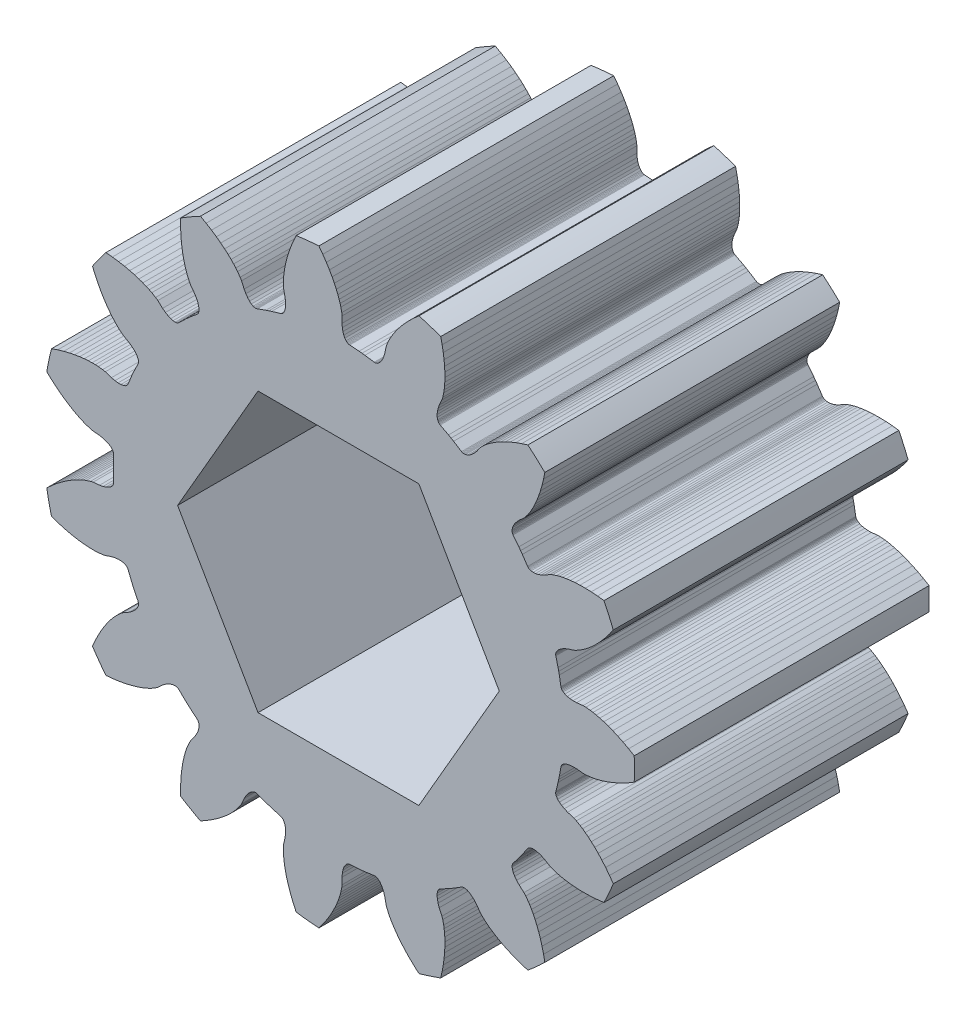
SolidWorks part; units mm, degrees
ref_plane "Front Plane" through (0, 0, 0) normal (0, 0, 1) x (1, 0, 0)
ref_plane "Top Plane" through (0, 0, 0) normal (0, 1, 0) x (1, 0, 0)
ref_plane "Right Plane" through (0, 0, 0) normal (1, 0, 0) x (0, 0, -1)
sketch "Model" plane through (0, 0, 0) normal (0, 0, 1) x (1, 0, 0)
  line L0 (11.6767, 4.5035) -> (11.5103, 4.2885)
  line L1 (11.5103, 4.2885) -> (11.3474, 4.0954)
  line L2 (11.3474, 4.0954) -> (11.1891, 3.9228)
  line L3 (11.1891, 3.9228) -> (11.0382, 3.7715)
  line L4 (11.0382, 3.7715) -> (10.8925, 3.6371)
  line L5 (10.8925, 3.6371) -> (10.7549, 3.5206)
  line L6 (10.7549, 3.5206) -> (10.6294, 3.4231)
  line L7 (10.6294, 3.4231) -> (10.5151, 3.3416)
  line L8 (10.5151, 3.3416) -> (10.4119, 3.2743)
  line L9 (10.4119, 3.2743) -> (10.2465, 3.1803)
  line L10 (10.2465, 3.1803) -> (10.1399, 3.1309)
  line L11 (10.1399, 3.1309) -> (9.873, 3.0467)
  line L12 (9.873, 3.0467) -> (9.7318, 2.9862)
  line L13 (9.7318, 2.9862) -> (9.613, 2.9201)
  line L14 (9.613, 2.9201) -> (9.5168, 2.8501)
  line L15 (9.5168, 2.8501) -> (9.4433, 2.778)
  line L16 (9.4433, 2.778) -> (9.3924, 2.7056)
  line L17 (9.3924, 2.7056) -> (9.3754, 2.6698)
  line L18 (9.3754, 2.6698) -> (9.364, 2.6346)
  line L19 (9.364, 2.6346) -> (9.3582, 2.6002)
  line L20 (9.3582, 2.6002) -> (9.3579, 2.5668)
  line L21 (9.3579, 2.5668) -> (9.363, 2.5346)
  line L22 (9.363, 2.5346) -> (9.4607, 2.1415)
  line L23 (9.4607, 2.1415) -> (9.488, 2.0167)
  line L24 (9.488, 2.0167) -> (9.5138, 1.8917)
  line L25 (9.5138, 1.8917) -> (9.5845, 1.4928)
  line L26 (9.5845, 1.4928) -> (9.5928, 1.4613)
  line L27 (9.5928, 1.4613) -> (9.6067, 1.4309)
  line L28 (9.6067, 1.4309) -> (9.626, 1.4019)
  line L29 (9.626, 1.4019) -> (9.6508, 1.3743)
  line L30 (9.6508, 1.3743) -> (9.6808, 1.3485)
  line L31 (9.6808, 1.3485) -> (9.7568, 1.3031)
  line L32 (9.7568, 1.3031) -> (9.8533, 1.2671)
  line L33 (9.8533, 1.2671) -> (9.9696, 1.2423)
  line L34 (9.9696, 1.2423) -> (10.105, 1.2303)
  line L35 (10.105, 1.2303) -> (10.2586, 1.2324)
  line L36 (10.2586, 1.2324) -> (10.5367, 1.2641)
  line L37 (10.5367, 1.2641) -> (10.6542, 1.2623)
  line L38 (10.6542, 1.2623) -> (10.8435, 1.2437)
  line L39 (10.8435, 1.2437) -> (10.9652, 1.2242)
  line L40 (10.9652, 1.2242) -> (11.1027, 1.1962)
  line L41 (11.1027, 1.1962) -> (11.2571, 1.1582)
  line L42 (11.2571, 1.1582) -> (11.4301, 1.1077)
  line L43 (11.4301, 1.1077) -> (11.6179, 1.0442)
  line L44 (11.6179, 1.0442) -> (11.8173, 0.9674)
  line L45 (11.8173, 0.9674) -> (12.0321, 0.8741)
  line L46 (12.0321, 0.8741) -> (12.2594, 0.764)
  line L47 (12.2594, 0.764) -> (12.499, 0.6352)
  line L48 (12.499, 0.6352) -> (12.7405, 0.492)
  line L49 (12.7405, -0.492) -> (12.499, -0.6352)
  line L50 (12.499, -0.6352) -> (12.2594, -0.764)
  line L51 (12.2594, -0.764) -> (12.0321, -0.8741)
  line L52 (12.0321, -0.8741) -> (11.8173, -0.9674)
  line L53 (11.8173, -0.9674) -> (11.6179, -1.0442)
  line L54 (11.6179, -1.0442) -> (11.4301, -1.1077)
  line L55 (11.4301, -1.1077) -> (11.2571, -1.1582)
  line L56 (11.2571, -1.1582) -> (11.1027, -1.1962)
  line L57 (11.1027, -1.1962) -> (10.9652, -1.2242)
  line L58 (10.9652, -1.2242) -> (10.8435, -1.2437)
  line L59 (10.8435, -1.2437) -> (10.6542, -1.2623)
  line L60 (10.6542, -1.2623) -> (10.5367, -1.2641)
  line L61 (10.5367, -1.2641) -> (10.2586, -1.2324)
  line L62 (10.2586, -1.2324) -> (10.105, -1.2303)
  line L63 (10.105, -1.2303) -> (9.9696, -1.2423)
  line L64 (9.9696, -1.2423) -> (9.8533, -1.2671)
  line L65 (9.8533, -1.2671) -> (9.7568, -1.3031)
  line L66 (9.7568, -1.3031) -> (9.6808, -1.3485)
  line L67 (9.6808, -1.3485) -> (9.6508, -1.3743)
  line L68 (9.6508, -1.3743) -> (9.626, -1.4019)
  line L69 (9.626, -1.4019) -> (9.6067, -1.4309)
  line L70 (9.6067, -1.4309) -> (9.5928, -1.4613)
  line L71 (9.5928, -1.4613) -> (9.5845, -1.4928)
  line L72 (9.5845, -1.4928) -> (9.5138, -1.8917)
  line L73 (9.5138, -1.8917) -> (9.488, -2.0167)
  line L74 (9.488, -2.0167) -> (9.4607, -2.1415)
  line L75 (9.4607, -2.1415) -> (9.363, -2.5346)
  line L76 (9.363, -2.5346) -> (9.3579, -2.5668)
  line L77 (9.3579, -2.5668) -> (9.3582, -2.6002)
  line L78 (9.3582, -2.6002) -> (9.364, -2.6346)
  line L79 (9.364, -2.6346) -> (9.3754, -2.6698)
  line L80 (9.3754, -2.6698) -> (9.3924, -2.7056)
  line L81 (9.3924, -2.7056) -> (9.4433, -2.778)
  line L82 (9.4433, -2.778) -> (9.5168, -2.8501)
  line L83 (9.5168, -2.8501) -> (9.613, -2.9201)
  line L84 (9.613, -2.9201) -> (9.7318, -2.9862)
  line L85 (9.7318, -2.9862) -> (9.873, -3.0467)
  line L86 (9.873, -3.0467) -> (10.1399, -3.1309)
  line L87 (10.1399, -3.1309) -> (10.2465, -3.1803)
  line L88 (10.2465, -3.1803) -> (10.4119, -3.2743)
  line L89 (10.4119, -3.2743) -> (10.5151, -3.3416)
  line L90 (10.5151, -3.3416) -> (10.6294, -3.4231)
  line L91 (10.6294, -3.4231) -> (10.7549, -3.5206)
  line L92 (10.7549, -3.5206) -> (10.8925, -3.6371)
  line L93 (10.8925, -3.6371) -> (11.0382, -3.7715)
  line L94 (11.0382, -3.7715) -> (11.1891, -3.9228)
  line L95 (11.1891, -3.9228) -> (11.3474, -4.0954)
  line L96 (11.3474, -4.0954) -> (11.5103, -4.2885)
  line L97 (11.5103, -4.2885) -> (11.6767, -4.5035)
  line L98 (11.6767, -4.5035) -> (11.8391, -4.7326)
  line L99 (11.4389, -5.6315) -> (11.16, -5.6641)
  line L100 (11.16, -5.6641) -> (10.8888, -5.6843)
  line L101 (10.8888, -5.6843) -> (10.6364, -5.6925)
  line L102 (10.6364, -5.6925) -> (10.4021, -5.6903)
  line L103 (10.4021, -5.6903) -> (10.1888, -5.6793)
  line L104 (10.1888, -5.6793) -> (9.9914, -5.661)
  line L105 (9.9914, -5.661) -> (9.8128, -5.6367)
  line L106 (9.8128, -5.6367) -> (9.6563, -5.6087)
  line L107 (9.6563, -5.6087) -> (9.5193, -5.5783)
  line L108 (9.5193, -5.5783) -> (9.4002, -5.5466)
  line L109 (9.4002, -5.5466) -> (9.2197, -5.4866)
  line L110 (9.2197, -5.4866) -> (9.1116, -5.4405)
  line L111 (9.1116, -5.4405) -> (8.8704, -5.2984)
  line L112 (8.8704, -5.2984) -> (8.731, -5.234)
  line L113 (8.731, -5.234) -> (8.6024, -5.1899)
  line L114 (8.6024, -5.1899) -> (8.486, -5.1653)
  line L115 (8.486, -5.1653) -> (8.3833, -5.1589)
  line L116 (8.3833, -5.1589) -> (8.2954, -5.1695)
  line L117 (8.2954, -5.1695) -> (8.2574, -5.1808)
  line L118 (8.2574, -5.1808) -> (8.2236, -5.1959)
  line L119 (8.2236, -5.1959) -> (8.1941, -5.2146)
  line L120 (8.1941, -5.2146) -> (8.1691, -5.2367)
  line L121 (8.1691, -5.2367) -> (8.1487, -5.2621)
  line L122 (8.1487, -5.2621) -> (7.9219, -5.5977)
  line L123 (7.9219, -5.5977) -> (7.8475, -5.7015)
  line L124 (7.8475, -5.7015) -> (7.7717, -5.8044)
  line L125 (7.7717, -5.8044) -> (7.5226, -6.1238)
  line L126 (7.5226, -6.1238) -> (7.5048, -6.151)
  line L127 (7.5048, -6.151) -> (7.4915, -6.1817)
  line L128 (7.4915, -6.1817) -> (7.4828, -6.2155)
  line L129 (7.4828, -6.2155) -> (7.4789, -6.2523)
  line L130 (7.4789, -6.2523) -> (7.4799, -6.2919)
  line L131 (7.4799, -6.2919) -> (7.4969, -6.3788)
  line L132 (7.4969, -6.3788) -> (7.5348, -6.4746)
  line L133 (7.5348, -6.4746) -> (7.5942, -6.5776)
  line L134 (7.5942, -6.5776) -> (7.6759, -6.6863)
  line L135 (7.6759, -6.6863) -> (7.7802, -6.799)
  line L136 (7.7802, -6.799) -> (7.9899, -6.9845)
  line L137 (7.9899, -6.9845) -> (8.0671, -7.073)
  line L138 (8.0671, -7.073) -> (8.1799, -7.2261)
  line L139 (8.1799, -7.2261) -> (8.2469, -7.3296)
  line L140 (8.2469, -7.3296) -> (8.3182, -7.4505)
  line L141 (8.3182, -7.4505) -> (8.3931, -7.5907)
  line L142 (8.3931, -7.5907) -> (8.4714, -7.753)
  line L143 (8.4714, -7.753) -> (8.5499, -7.9351)
  line L144 (8.5499, -7.9351) -> (8.6262, -8.1346)
  line L145 (8.6262, -8.1346) -> (8.7007, -8.3567)
  line L146 (8.7007, -8.3567) -> (8.7709, -8.5993)
  line L147 (8.7709, -8.5993) -> (8.8355, -8.8635)
  line L148 (8.8355, -8.8635) -> (8.8906, -9.1388)
  line L149 (8.1594, -9.7972) -> (7.8914, -9.7136)
  line L150 (7.8914, -9.7136) -> (7.6354, -9.6217)
  line L151 (7.6354, -9.6217) -> (7.4015, -9.5265)
  line L152 (7.4015, -9.5265) -> (7.1884, -9.4292)
  line L153 (7.1884, -9.4292) -> (6.9979, -9.3325)
  line L154 (6.9979, -9.3325) -> (6.8251, -9.2354)
  line L155 (6.8251, -9.2354) -> (6.6718, -9.1406)
  line L156 (6.6718, -9.1406) -> (6.5402, -9.0514)
  line L157 (6.5402, -9.0514) -> (6.4274, -8.9679)
  line L158 (6.4274, -8.9679) -> (6.3315, -8.8905)
  line L159 (6.3315, -8.8905) -> (6.191, -8.7623)
  line L160 (6.191, -8.7623) -> (6.111, -8.6762)
  line L161 (6.111, -8.6762) -> (5.9485, -8.4483)
  line L162 (5.9485, -8.4483) -> (5.8473, -8.3327)
  line L163 (5.8473, -8.3327) -> (5.7478, -8.2402)
  line L164 (5.7478, -8.2402) -> (5.6515, -8.1703)
  line L165 (5.6515, -8.1703) -> (5.5602, -8.1226)
  line L166 (5.5602, -8.1226) -> (5.4756, -8.0966)
  line L167 (5.4756, -8.0966) -> (5.4363, -8.0915)
  line L168 (5.4363, -8.0915) -> (5.3993, -8.0916)
  line L169 (5.3993, -8.0916) -> (5.3647, -8.0966)
  line L170 (5.3647, -8.0966) -> (5.3329, -8.1067)
  line L171 (5.3329, -8.1067) -> (5.3039, -8.1215)
  line L172 (5.3039, -8.1215) -> (4.9602, -8.3359)
  line L173 (4.9602, -8.3359) -> (4.85, -8.4004)
  line L174 (4.85, -8.4004) -> (4.739, -8.4636)
  line L175 (4.739, -8.4636) -> (4.3815, -8.6541)
  line L176 (4.3815, -8.6541) -> (4.3542, -8.6717)
  line L177 (4.3542, -8.6717) -> (4.3295, -8.6943)
  line L178 (4.3295, -8.6943) -> (4.3078, -8.7217)
  line L179 (4.3078, -8.7217) -> (4.2893, -8.7537)
  line L180 (4.2893, -8.7537) -> (4.2741, -8.7903)
  line L181 (4.2741, -8.7903) -> (4.2543, -8.8766)
  line L182 (4.2543, -8.8766) -> (4.2499, -8.9795)
  line L183 (4.2499, -8.9795) -> (4.2623, -9.0978)
  line L184 (4.2623, -9.0978) -> (4.2927, -9.2303)
  line L185 (4.2927, -9.2303) -> (4.3422, -9.3757)
  line L186 (4.3422, -9.3757) -> (4.4583, -9.6304)
  line L187 (4.4583, -9.6304) -> (4.4928, -9.7427)
  line L188 (4.4928, -9.7427) -> (4.5336, -9.9285)
  line L189 (4.5336, -9.9285) -> (4.5527, -10.0502)
  line L190 (4.5527, -10.0502) -> (4.5686, -10.1897)
  line L191 (4.5686, -10.1897) -> (4.5801, -10.3482)
  line L192 (4.5801, -10.3482) -> (4.5856, -10.5284)
  line L193 (4.5856, -10.5284) -> (4.5832, -10.7266)
  line L194 (4.5832, -10.7266) -> (4.5718, -10.94)
  line L195 (4.5718, -10.94) -> (4.5495, -11.1731)
  line L196 (4.5495, -11.1731) -> (4.5149, -11.4233)
  line L197 (4.5149, -11.4233) -> (4.4665, -11.691)
  line L198 (4.4665, -11.691) -> (4.4049, -11.9649)
  line L199 (3.4691, -12.2689) -> (3.2583, -12.0835)
  line L200 (3.2583, -12.0835) -> (3.0618, -11.8955)
  line L201 (3.0618, -11.8955) -> (2.8868, -11.7134)
  line L202 (2.8868, -11.7134) -> (2.7317, -11.5378)
  line L203 (2.7317, -11.5378) -> (2.597, -11.3719)
  line L204 (2.597, -11.3719) -> (2.4786, -11.213)
  line L205 (2.4786, -11.213) -> (2.3771, -11.064)
  line L206 (2.3771, -11.064) -> (2.2932, -10.929)
  line L207 (2.2932, -10.929) -> (2.2242, -10.8068)
  line L208 (2.2242, -10.8068) -> (2.168, -10.6971)
  line L209 (2.168, -10.6971) -> (2.0918, -10.5228)
  line L210 (2.0918, -10.5228) -> (2.0538, -10.4117)
  line L211 (2.0538, -10.4117) -> (1.998, -10.1374)
  line L212 (1.998, -10.1374) -> (1.9526, -9.9906)
  line L213 (1.9526, -9.9906) -> (1.8993, -9.8656)
  line L214 (1.8993, -9.8656) -> (1.8397, -9.7626)
  line L215 (1.8397, -9.7626) -> (1.7757, -9.6819)
  line L216 (1.7757, -9.6819) -> (1.709, -9.6238)
  line L217 (1.709, -9.6238) -> (1.6752, -9.6031)
  line L218 (1.6752, -9.6031) -> (1.6414, -9.5881)
  line L219 (1.6414, -9.5881) -> (1.6077, -9.5787)
  line L220 (1.6077, -9.5787) -> (1.5745, -9.5749)
  line L221 (1.5745, -9.5749) -> (1.542, -9.5767)
  line L222 (1.542, -9.5767) -> (1.1409, -9.6327)
  line L223 (1.1409, -9.6327) -> (1.0139, -9.6469)
  line L224 (1.0139, -9.6469) -> (0.8868, -9.6594)
  line L225 (0.8868, -9.6594) -> (0.4828, -9.688)
  line L226 (0.4828, -9.688) -> (0.4506, -9.693)
  line L227 (0.4506, -9.693) -> (0.4189, -9.7036)
  line L228 (0.4189, -9.7036) -> (0.388, -9.7198)
  line L229 (0.388, -9.7198) -> (0.358, -9.7415)
  line L230 (0.358, -9.7415) -> (0.3292, -9.7688)
  line L231 (0.3292, -9.7688) -> (0.2761, -9.8396)
  line L232 (0.2761, -9.8396) -> (0.2302, -9.9318)
  line L233 (0.2302, -9.9318) -> (0.1934, -10.0449)
  line L234 (0.1934, -10.0449) -> (0.1672, -10.1783)
  line L235 (0.1672, -10.1783) -> (0.1534, -10.3312)
  line L236 (0.1534, -10.3312) -> (0.1558, -10.6111)
  line L237 (0.1558, -10.6111) -> (0.1417, -10.7278)
  line L238 (0.1417, -10.7278) -> (0.1034, -10.9141)
  line L239 (0.1034, -10.9141) -> (0.0713, -11.0331)
  line L240 (0.0713, -11.0331) -> (0.0291, -11.1669)
  line L241 (0.0291, -11.1669) -> (-0.0249, -11.3165)
  line L242 (-0.0249, -11.3165) -> (-0.0932, -11.4833)
  line L243 (-0.0932, -11.4833) -> (-0.1759, -11.6634)
  line L244 (-0.1759, -11.6634) -> (-0.2732, -11.8536)
  line L245 (-0.2732, -11.8536) -> (-0.3884, -12.0576)
  line L246 (-0.3884, -12.0576) -> (-0.5217, -12.2721)
  line L247 (-0.5217, -12.2721) -> (-0.6748, -12.4969)
  line L248 (-0.6748, -12.4969) -> (-0.8425, -12.7221)
  line L249 (-1.821, -12.6193) -> (-1.9382, -12.3641)
  line L250 (-1.9382, -12.3641) -> (-2.0412, -12.1124)
  line L251 (-2.0412, -12.1124) -> (-2.127, -11.8749)
  line L252 (-2.127, -11.8749) -> (-2.1973, -11.6514)
  line L253 (-2.1973, -11.6514) -> (-2.2529, -11.4451)
  line L254 (-2.2529, -11.4451) -> (-2.2964, -11.2517)
  line L255 (-2.2964, -11.2517) -> (-2.3285, -11.0743)
  line L256 (-2.3285, -11.0743) -> (-2.3502, -10.9169)
  line L257 (-2.3502, -10.9169) -> (-2.3637, -10.7771)
  line L258 (-2.3637, -10.7771) -> (-2.3703, -10.6541)
  line L259 (-2.3703, -10.6541) -> (-2.369, -10.4639)
  line L260 (-2.369, -10.4639) -> (-2.3586, -10.3469)
  line L261 (-2.3586, -10.3469) -> (-2.298, -10.0736)
  line L262 (-2.298, -10.0736) -> (-2.2798, -9.9211)
  line L263 (-2.2798, -9.9211) -> (-2.2776, -9.7852)
  line L264 (-2.2776, -9.7852) -> (-2.2901, -9.6669)
  line L265 (-2.2901, -9.6669) -> (-2.3158, -9.5671)
  line L266 (-2.3158, -9.5671) -> (-2.3531, -9.4868)
  line L267 (-2.3531, -9.4868) -> (-2.3756, -9.4542)
  line L268 (-2.3756, -9.4542) -> (-2.4004, -9.4268)
  line L269 (-2.4004, -9.4268) -> (-2.4273, -9.4045)
  line L270 (-2.4273, -9.4045) -> (-2.456, -9.3875)
  line L271 (-2.456, -9.3875) -> (-2.4865, -9.3759)
  line L272 (-2.4865, -9.3759) -> (-2.8758, -9.2639)
  line L273 (-2.8758, -9.2639) -> (-2.9975, -9.2252)
  line L274 (-2.9975, -9.2252) -> (-3.1187, -9.185)
  line L275 (-3.1187, -9.185) -> (-3.4994, -9.0468)
  line L276 (-3.4994, -9.0468) -> (-3.5309, -9.0383)
  line L277 (-3.5309, -9.0383) -> (-3.5641, -9.0351)
  line L278 (-3.5641, -9.0351) -> (-3.599, -9.0373)
  line L279 (-3.599, -9.0373) -> (-3.6352, -9.045)
  line L280 (-3.6352, -9.045) -> (-3.6725, -9.0581)
  line L281 (-3.6725, -9.0581) -> (-3.7499, -9.1012)
  line L282 (-3.7499, -9.1012) -> (-3.8293, -9.1668)
  line L283 (-3.8293, -9.1668) -> (-3.9089, -9.2551)
  line L284 (-3.9089, -9.2551) -> (-3.9871, -9.3664)
  line L285 (-3.9871, -9.3664) -> (-4.062, -9.5004)
  line L286 (-4.062, -9.5004) -> (-4.1736, -9.7571)
  line L287 (-4.1736, -9.7571) -> (-4.234, -9.858)
  line L288 (-4.234, -9.858) -> (-4.3447, -10.0126)
  line L289 (-4.3447, -10.0126) -> (-4.4224, -10.1082)
  line L290 (-4.4224, -10.1082) -> (-4.5154, -10.2134)
  line L291 (-4.5154, -10.2134) -> (-4.6255, -10.328)
  line L292 (-4.6255, -10.328) -> (-4.7558, -10.4526)
  line L293 (-4.7558, -10.4526) -> (-4.9046, -10.5835)
  line L294 (-4.9046, -10.5835) -> (-5.0709, -10.7177)
  line L295 (-5.0709, -10.7177) -> (-5.2591, -10.8572)
  line L296 (-5.2591, -10.8572) -> (-5.4681, -10.999)
  line L297 (-5.4681, -10.999) -> (-5.6994, -11.142)
  line L298 (-5.6994, -11.142) -> (-5.9442, -11.2796)
  line L299 (-6.7963, -10.7876) -> (-6.7996, -10.5068)
  line L300 (-6.7996, -10.5068) -> (-6.7913, -10.235)
  line L301 (-6.7913, -10.235) -> (-6.7731, -9.9831)
  line L302 (-6.7731, -9.9831) -> (-6.7464, -9.7504)
  line L303 (-6.7464, -9.7504) -> (-6.7132, -9.5393)
  line L304 (-6.7132, -9.5393) -> (-6.6743, -9.3449)
  line L305 (-6.6743, -9.3449) -> (-6.6315, -9.1698)
  line L306 (-6.6315, -9.1698) -> (-6.5873, -9.0171)
  line L307 (-6.5873, -9.0171) -> (-6.5428, -8.884)
  line L308 (-6.5428, -8.884) -> (-6.4988, -8.7689)
  line L309 (-6.4988, -8.7689) -> (-6.4203, -8.5957)
  line L310 (-6.4203, -8.5957) -> (-6.3631, -8.493)
  line L311 (-6.3631, -8.493) -> (-6.1966, -8.268)
  line L312 (-6.1966, -8.268) -> (-6.118, -8.1361)
  line L313 (-6.118, -8.1361) -> (-6.0607, -8.0128)
  line L314 (-6.0607, -8.0128) -> (-6.024, -7.8996)
  line L315 (-6.024, -7.8996) -> (-6.0069, -7.7981)
  line L316 (-6.0069, -7.7981) -> (-6.0083, -7.7096)
  line L317 (-6.0083, -7.7096) -> (-6.0156, -7.6706)
  line L318 (-6.0156, -7.6706) -> (-6.0271, -7.6354)
  line L319 (-6.0271, -7.6354) -> (-6.0426, -7.6042)
  line L320 (-6.0426, -7.6042) -> (-6.062, -7.577)
  line L321 (-6.062, -7.577) -> (-6.0851, -7.554)
  line L322 (-6.0851, -7.554) -> (-6.3951, -7.2934)
  line L323 (-6.3951, -7.2934) -> (-6.4906, -7.2085)
  line L324 (-6.4906, -7.2085) -> (-6.5849, -7.1224)
  line L325 (-6.5849, -7.1224) -> (-6.8765, -6.8413)
  line L326 (-6.8765, -6.8413) -> (-6.9018, -6.8208)
  line L327 (-6.9018, -6.8208) -> (-6.9309, -6.8043)
  line L328 (-6.9309, -6.8043) -> (-6.9636, -6.7922)
  line L329 (-6.9636, -6.7922) -> (-6.9998, -6.7844)
  line L330 (-6.9998, -6.7844) -> (-7.0393, -6.7813)
  line L331 (-7.0393, -6.7813) -> (-7.1275, -6.7891)
  line L332 (-7.1275, -6.7891) -> (-7.2267, -6.8167)
  line L333 (-7.2267, -6.8167) -> (-7.3354, -6.8651)
  line L334 (-7.3354, -6.8651) -> (-7.452, -6.9349)
  line L335 (-7.452, -6.9349) -> (-7.575, -7.0269)
  line L336 (-7.575, -7.0269) -> (-7.7814, -7.216)
  line L337 (-7.7814, -7.216) -> (-7.8775, -7.2836)
  line L338 (-7.8775, -7.2836) -> (-8.0416, -7.3798)
  line L339 (-8.0416, -7.3798) -> (-8.1515, -7.4356)
  line L340 (-8.1515, -7.4356) -> (-8.2792, -7.4938)
  line L341 (-8.2792, -7.4938) -> (-8.4264, -7.5537)
  line L342 (-8.4264, -7.5537) -> (-8.5961, -7.6146)
  line L343 (-8.5961, -7.6146) -> (-8.7853, -7.6736)
  line L344 (-8.7853, -7.6736) -> (-8.9918, -7.7286)
  line L345 (-8.9918, -7.7286) -> (-9.2204, -7.7795)
  line L346 (-9.2204, -7.7795) -> (-9.469, -7.824)
  line L347 (-9.469, -7.824) -> (-9.7385, -7.8606)
  line L348 (-9.7385, -7.8606) -> (-10.0181, -7.8867)
  line L349 (-10.5964, -7.0906) -> (-10.4852, -6.8328)
  line L350 (-10.4852, -6.8328) -> (-10.3671, -6.5879)
  line L351 (-10.3671, -6.5879) -> (-10.248, -6.3651)
  line L352 (-10.248, -6.3651) -> (-10.129, -6.1634)
  line L353 (-10.129, -6.1634) -> (-10.0128, -5.984)
  line L354 (-10.0128, -5.984) -> (-9.8982, -5.8223)
  line L355 (-9.8982, -5.8223) -> (-9.7879, -5.6798)
  line L356 (-9.7879, -5.6798) -> (-9.6854, -5.5582)
  line L357 (-9.6854, -5.5582) -> (-9.5906, -5.4548)
  line L358 (-9.5906, -5.4548) -> (-9.5036, -5.3675)
  line L359 (-9.5036, -5.3675) -> (-9.3614, -5.2412)
  line L360 (-9.3614, -5.2412) -> (-9.2674, -5.1707)
  line L361 (-9.2674, -5.1707) -> (-9.0238, -5.0328)
  line L362 (-9.0238, -5.0328) -> (-8.8983, -4.9443)
  line L363 (-8.8983, -4.9443) -> (-8.7958, -4.855)
  line L364 (-8.7958, -4.855) -> (-8.7163, -4.7665)
  line L365 (-8.7163, -4.7665) -> (-8.6593, -4.6807)
  line L366 (-8.6593, -4.6807) -> (-8.6246, -4.5993)
  line L367 (-8.6246, -4.5993) -> (-8.6154, -4.5607)
  line L368 (-8.6154, -4.5607) -> (-8.6116, -4.5239)
  line L369 (-8.6116, -4.5239) -> (-8.6131, -4.489)
  line L370 (-8.6131, -4.489) -> (-8.6197, -4.4563)
  line L371 (-8.6197, -4.4563) -> (-8.6315, -4.4259)
  line L372 (-8.6315, -4.4259) -> (-8.8087, -4.0617)
  line L373 (-8.8087, -4.0617) -> (-8.8614, -3.9453)
  line L374 (-8.8614, -3.9453) -> (-8.9126, -3.8283)
  line L375 (-8.9126, -3.8283) -> (-9.0646, -3.4529)
  line L376 (-9.0646, -3.4529) -> (-9.0794, -3.4239)
  line L377 (-9.0794, -3.4239) -> (-9.0993, -3.397)
  line L378 (-9.0993, -3.397) -> (-9.1242, -3.3726)
  line L379 (-9.1242, -3.3726) -> (-9.1541, -3.3508)
  line L380 (-9.1541, -3.3508) -> (-9.1889, -3.3318)
  line L381 (-9.1889, -3.3318) -> (-9.2727, -3.3032)
  line L382 (-9.2727, -3.3032) -> (-9.3745, -3.2881)
  line L383 (-9.3745, -3.2881) -> (-9.4935, -3.288)
  line L384 (-9.4935, -3.288) -> (-9.6284, -3.3043)
  line L385 (-9.6284, -3.3043) -> (-9.7782, -3.3384)
  line L386 (-9.7782, -3.3384) -> (-10.0437, -3.4272)
  line L387 (-10.0437, -3.4272) -> (-10.159, -3.4498)
  line L388 (-10.159, -3.4498) -> (-10.348, -3.471)
  line L389 (-10.348, -3.471) -> (-10.471, -3.4772)
  line L390 (-10.471, -3.4772) -> (-10.6114, -3.4785)
  line L391 (-10.6114, -3.4785) -> (-10.7703, -3.4733)
  line L392 (-10.7703, -3.4733) -> (-10.95, -3.4599)
  line L393 (-10.95, -3.4599) -> (-11.1469, -3.4369)
  line L394 (-11.1469, -3.4369) -> (-11.3579, -3.4032)
  line L395 (-11.3579, -3.4032) -> (-11.5875, -3.3566)
  line L396 (-11.5875, -3.3566) -> (-11.8327, -3.2961)
  line L397 (-11.8327, -3.2961) -> (-12.0938, -3.22)
  line L398 (-12.0938, -3.22) -> (-12.3598, -3.1301)
  line L399 (-12.5643, -2.1677) -> (-12.3579, -1.9774)
  line L400 (-12.3579, -1.9774) -> (-12.1504, -1.8016)
  line L401 (-12.1504, -1.8016) -> (-11.951, -1.6466)
  line L402 (-11.951, -1.6466) -> (-11.7602, -1.5107)
  line L403 (-11.7602, -1.5107) -> (-11.5811, -1.3941)
  line L404 (-11.5811, -1.3941) -> (-11.4106, -1.293)
  line L405 (-11.4106, -1.293) -> (-11.2519, -1.2076)
  line L406 (-11.2519, -1.2076) -> (-11.1088, -1.1383)
  line L407 (-11.1088, -1.1383) -> (-10.9801, -1.0823)
  line L408 (-10.9801, -1.0823) -> (-10.8651, -1.038)
  line L409 (-10.8651, -1.038) -> (-10.6838, -0.9805)
  line L410 (-10.6838, -0.9805) -> (-10.5693, -0.9542)
  line L411 (-10.5693, -0.9542) -> (-10.2907, -0.9274)
  line L412 (-10.2907, -0.9274) -> (-10.14, -0.8976)
  line L413 (-10.14, -0.8976) -> (-10.0101, -0.8576)
  line L414 (-10.0101, -0.8576) -> (-9.9014, -0.8092)
  line L415 (-9.9014, -0.8092) -> (-9.8145, -0.754)
  line L416 (-9.8145, -0.754) -> (-9.7497, -0.6937)
  line L417 (-9.7497, -0.6937) -> (-9.7256, -0.6622)
  line L418 (-9.7256, -0.6622) -> (-9.7071, -0.6301)
  line L419 (-9.7071, -0.6301) -> (-9.6943, -0.5977)
  line L420 (-9.6943, -0.5977) -> (-9.687, -0.5651)
  line L421 (-9.687, -0.5651) -> (-9.6854, -0.5325)
  line L422 (-9.6854, -0.5325) -> (-9.6992, -0.1277)
  line L423 (-9.6992, -0.1277) -> (-9.7, 0)
  line L424 (-9.7, 0) -> (-9.6992, 0.1277)
  line L425 (-9.6992, 0.1277) -> (-9.6854, 0.5325)
  line L426 (-9.6854, 0.5325) -> (-9.687, 0.5651)
  line L427 (-9.687, 0.5651) -> (-9.6943, 0.5977)
  line L428 (-9.6943, 0.5977) -> (-9.7071, 0.6301)
  line L429 (-9.7071, 0.6301) -> (-9.7256, 0.6622)
  line L430 (-9.7256, 0.6622) -> (-9.7497, 0.6937)
  line L431 (-9.7497, 0.6937) -> (-9.8145, 0.754)
  line L432 (-9.8145, 0.754) -> (-9.9014, 0.8092)
  line L433 (-9.9014, 0.8092) -> (-10.0101, 0.8576)
  line L434 (-10.0101, 0.8576) -> (-10.14, 0.8976)
  line L435 (-10.14, 0.8976) -> (-10.2907, 0.9274)
  line L436 (-10.2907, 0.9274) -> (-10.5693, 0.9542)
  line L437 (-10.5693, 0.9542) -> (-10.6838, 0.9805)
  line L438 (-10.6838, 0.9805) -> (-10.8651, 1.038)
  line L439 (-10.8651, 1.038) -> (-10.9801, 1.0823)
  line L440 (-10.9801, 1.0823) -> (-11.1088, 1.1383)
  line L441 (-11.1088, 1.1383) -> (-11.2519, 1.2076)
  line L442 (-11.2519, 1.2076) -> (-11.4106, 1.293)
  line L443 (-11.4106, 1.293) -> (-11.5811, 1.3941)
  line L444 (-11.5811, 1.3941) -> (-11.7602, 1.5107)
  line L445 (-11.7602, 1.5107) -> (-11.951, 1.6466)
  line L446 (-11.951, 1.6466) -> (-12.1504, 1.8016)
  line L447 (-12.1504, 1.8016) -> (-12.3579, 1.9774)
  line L448 (-12.3579, 1.9774) -> (-12.5643, 2.1677)
  line L449 (-12.3598, 3.1301) -> (-12.0938, 3.22)
  line L450 (-12.0938, 3.22) -> (-11.8327, 3.2961)
  line L451 (-11.8327, 3.2961) -> (-11.5875, 3.3566)
  line L452 (-11.5875, 3.3566) -> (-11.3579, 3.4032)
  line L453 (-11.3579, 3.4032) -> (-11.1469, 3.4369)
  line L454 (-11.1469, 3.4369) -> (-10.95, 3.4599)
  line L455 (-10.95, 3.4599) -> (-10.7703, 3.4733)
  line L456 (-10.7703, 3.4733) -> (-10.6114, 3.4785)
  line L457 (-10.6114, 3.4785) -> (-10.471, 3.4772)
  line L458 (-10.471, 3.4772) -> (-10.348, 3.471)
  line L459 (-10.348, 3.471) -> (-10.159, 3.4498)
  line L460 (-10.159, 3.4498) -> (-10.0437, 3.4272)
  line L461 (-10.0437, 3.4272) -> (-9.7782, 3.3384)
  line L462 (-9.7782, 3.3384) -> (-9.6284, 3.3043)
  line L463 (-9.6284, 3.3043) -> (-9.4935, 3.288)
  line L464 (-9.4935, 3.288) -> (-9.3745, 3.2881)
  line L465 (-9.3745, 3.2881) -> (-9.2727, 3.3032)
  line L466 (-9.2727, 3.3032) -> (-9.1889, 3.3318)
  line L467 (-9.1889, 3.3318) -> (-9.1541, 3.3508)
  line L468 (-9.1541, 3.3508) -> (-9.1242, 3.3726)
  line L469 (-9.1242, 3.3726) -> (-9.0993, 3.397)
  line L470 (-9.0993, 3.397) -> (-9.0794, 3.4239)
  line L471 (-9.0794, 3.4239) -> (-9.0646, 3.4529)
  line L472 (-9.0646, 3.4529) -> (-8.9126, 3.8283)
  line L473 (-8.9126, 3.8283) -> (-8.8614, 3.9453)
  line L474 (-8.8614, 3.9453) -> (-8.8087, 4.0617)
  line L475 (-8.8087, 4.0617) -> (-8.6315, 4.4259)
  line L476 (-8.6315, 4.4259) -> (-8.6197, 4.4563)
  line L477 (-8.6197, 4.4563) -> (-8.6131, 4.489)
  line L478 (-8.6131, 4.489) -> (-8.6116, 4.5239)
  line L479 (-8.6116, 4.5239) -> (-8.6154, 4.5607)
  line L480 (-8.6154, 4.5607) -> (-8.6246, 4.5993)
  line L481 (-8.6246, 4.5993) -> (-8.6593, 4.6807)
  line L482 (-8.6593, 4.6807) -> (-8.7163, 4.7665)
  line L483 (-8.7163, 4.7665) -> (-8.7958, 4.855)
  line L484 (-8.7958, 4.855) -> (-8.8983, 4.9443)
  line L485 (-8.8983, 4.9443) -> (-9.0238, 5.0328)
  line L486 (-9.0238, 5.0328) -> (-9.2674, 5.1707)
  line L487 (-9.2674, 5.1707) -> (-9.3614, 5.2412)
  line L488 (-9.3614, 5.2412) -> (-9.5036, 5.3675)
  line L489 (-9.5036, 5.3675) -> (-9.5906, 5.4548)
  line L490 (-9.5906, 5.4548) -> (-9.6854, 5.5582)
  line L491 (-9.6854, 5.5582) -> (-9.7879, 5.6798)
  line L492 (-9.7879, 5.6798) -> (-9.8982, 5.8223)
  line L493 (-9.8982, 5.8223) -> (-10.0128, 5.984)
  line L494 (-10.0128, 5.984) -> (-10.129, 6.1634)
  line L495 (-10.129, 6.1634) -> (-10.248, 6.3651)
  line L496 (-10.248, 6.3651) -> (-10.3671, 6.5879)
  line L497 (-10.3671, 6.5879) -> (-10.4852, 6.8328)
  line L498 (-10.4852, 6.8328) -> (-10.5964, 7.0906)
  line L499 (-10.0181, 7.8867) -> (-9.7385, 7.8606)
  line L500 (-9.7385, 7.8606) -> (-9.469, 7.824)
  line L501 (-9.469, 7.824) -> (-9.2204, 7.7795)
  line L502 (-9.2204, 7.7795) -> (-8.9918, 7.7286)
  line L503 (-8.9918, 7.7286) -> (-8.7853, 7.6736)
  line L504 (-8.7853, 7.6736) -> (-8.5961, 7.6146)
  line L505 (-8.5961, 7.6146) -> (-8.4264, 7.5537)
  line L506 (-8.4264, 7.5537) -> (-8.2792, 7.4938)
  line L507 (-8.2792, 7.4938) -> (-8.1515, 7.4356)
  line L508 (-8.1515, 7.4356) -> (-8.0416, 7.3798)
  line L509 (-8.0416, 7.3798) -> (-7.8775, 7.2836)
  line L510 (-7.8775, 7.2836) -> (-7.7814, 7.216)
  line L511 (-7.7814, 7.216) -> (-7.575, 7.0269)
  line L512 (-7.575, 7.0269) -> (-7.452, 6.9349)
  line L513 (-7.452, 6.9349) -> (-7.3354, 6.8651)
  line L514 (-7.3354, 6.8651) -> (-7.2267, 6.8167)
  line L515 (-7.2267, 6.8167) -> (-7.1275, 6.7891)
  line L516 (-7.1275, 6.7891) -> (-7.0393, 6.7813)
  line L517 (-7.0393, 6.7813) -> (-6.9998, 6.7844)
  line L518 (-6.9998, 6.7844) -> (-6.9636, 6.7922)
  line L519 (-6.9636, 6.7922) -> (-6.9309, 6.8043)
  line L520 (-6.9309, 6.8043) -> (-6.9018, 6.8208)
  line L521 (-6.9018, 6.8208) -> (-6.8765, 6.8413)
  line L522 (-6.8765, 6.8413) -> (-6.5849, 7.1224)
  line L523 (-6.5849, 7.1224) -> (-6.4906, 7.2085)
  line L524 (-6.4906, 7.2085) -> (-6.3951, 7.2934)
  line L525 (-6.3951, 7.2934) -> (-6.0851, 7.554)
  line L526 (-6.0851, 7.554) -> (-6.062, 7.577)
  line L527 (-6.062, 7.577) -> (-6.0426, 7.6042)
  line L528 (-6.0426, 7.6042) -> (-6.0271, 7.6354)
  line L529 (-6.0271, 7.6354) -> (-6.0156, 7.6706)
  line L530 (-6.0156, 7.6706) -> (-6.0083, 7.7096)
  line L531 (-6.0083, 7.7096) -> (-6.0069, 7.7981)
  line L532 (-6.0069, 7.7981) -> (-6.024, 7.8996)
  line L533 (-6.024, 7.8996) -> (-6.0607, 8.0128)
  line L534 (-6.0607, 8.0128) -> (-6.118, 8.1361)
  line L535 (-6.118, 8.1361) -> (-6.1966, 8.268)
  line L536 (-6.1966, 8.268) -> (-6.3631, 8.493)
  line L537 (-6.3631, 8.493) -> (-6.4203, 8.5957)
  line L538 (-6.4203, 8.5957) -> (-6.4988, 8.7689)
  line L539 (-6.4988, 8.7689) -> (-6.5428, 8.884)
  line L540 (-6.5428, 8.884) -> (-6.5873, 9.0171)
  line L541 (-6.5873, 9.0171) -> (-6.6315, 9.1698)
  line L542 (-6.6315, 9.1698) -> (-6.6743, 9.3449)
  line L543 (-6.6743, 9.3449) -> (-6.7132, 9.5393)
  line L544 (-6.7132, 9.5393) -> (-6.7464, 9.7504)
  line L545 (-6.7464, 9.7504) -> (-6.7731, 9.9831)
  line L546 (-6.7731, 9.9831) -> (-6.7913, 10.235)
  line L547 (-6.7913, 10.235) -> (-6.7996, 10.5068)
  line L548 (-6.7996, 10.5068) -> (-6.7963, 10.7876)
  line L549 (-5.9442, 11.2796) -> (-5.6994, 11.142)
  line L550 (-5.6994, 11.142) -> (-5.4681, 10.999)
  line L551 (-5.4681, 10.999) -> (-5.2591, 10.8572)
  line L552 (-5.2591, 10.8572) -> (-5.0709, 10.7177)
  line L553 (-5.0709, 10.7177) -> (-4.9046, 10.5835)
  line L554 (-4.9046, 10.5835) -> (-4.7558, 10.4526)
  line L555 (-4.7558, 10.4526) -> (-4.6255, 10.328)
  line L556 (-4.6255, 10.328) -> (-4.5154, 10.2134)
  line L557 (-4.5154, 10.2134) -> (-4.4224, 10.1082)
  line L558 (-4.4224, 10.1082) -> (-4.3447, 10.0126)
  line L559 (-4.3447, 10.0126) -> (-4.234, 9.858)
  line L560 (-4.234, 9.858) -> (-4.1736, 9.7571)
  line L561 (-4.1736, 9.7571) -> (-4.062, 9.5004)
  line L562 (-4.062, 9.5004) -> (-3.9871, 9.3664)
  line L563 (-3.9871, 9.3664) -> (-3.9089, 9.2551)
  line L564 (-3.9089, 9.2551) -> (-3.8293, 9.1668)
  line L565 (-3.8293, 9.1668) -> (-3.7499, 9.1012)
  line L566 (-3.7499, 9.1012) -> (-3.6725, 9.0581)
  line L567 (-3.6725, 9.0581) -> (-3.6352, 9.045)
  line L568 (-3.6352, 9.045) -> (-3.599, 9.0373)
  line L569 (-3.599, 9.0373) -> (-3.5641, 9.0351)
  line L570 (-3.5641, 9.0351) -> (-3.5309, 9.0383)
  line L571 (-3.5309, 9.0383) -> (-3.4994, 9.0468)
  line L572 (-3.4994, 9.0468) -> (-3.1187, 9.185)
  line L573 (-3.1187, 9.185) -> (-2.9975, 9.2252)
  line L574 (-2.9975, 9.2252) -> (-2.8758, 9.2639)
  line L575 (-2.8758, 9.2639) -> (-2.4865, 9.3759)
  line L576 (-2.4865, 9.3759) -> (-2.456, 9.3875)
  line L577 (-2.456, 9.3875) -> (-2.4273, 9.4045)
  line L578 (-2.4273, 9.4045) -> (-2.4004, 9.4268)
  line L579 (-2.4004, 9.4268) -> (-2.3756, 9.4542)
  line L580 (-2.3756, 9.4542) -> (-2.3531, 9.4868)
  line L581 (-2.3531, 9.4868) -> (-2.3158, 9.5671)
  line L582 (-2.3158, 9.5671) -> (-2.2901, 9.6669)
  line L583 (-2.2901, 9.6669) -> (-2.2776, 9.7852)
  line L584 (-2.2776, 9.7852) -> (-2.2798, 9.9211)
  line L585 (-2.2798, 9.9211) -> (-2.298, 10.0736)
  line L586 (-2.298, 10.0736) -> (-2.3586, 10.3469)
  line L587 (-2.3586, 10.3469) -> (-2.369, 10.4639)
  line L588 (-2.369, 10.4639) -> (-2.3703, 10.6541)
  line L589 (-2.3703, 10.6541) -> (-2.3637, 10.7771)
  line L590 (-2.3637, 10.7771) -> (-2.3502, 10.9169)
  line L591 (-2.3502, 10.9169) -> (-2.3285, 11.0743)
  line L592 (-2.3285, 11.0743) -> (-2.2964, 11.2517)
  line L593 (-2.2964, 11.2517) -> (-2.2529, 11.4451)
  line L594 (-2.2529, 11.4451) -> (-2.1973, 11.6514)
  line L595 (-2.1973, 11.6514) -> (-2.127, 11.8749)
  line L596 (-2.127, 11.8749) -> (-2.0412, 12.1124)
  line L597 (-2.0412, 12.1124) -> (-1.9382, 12.3641)
  line L598 (-1.9382, 12.3641) -> (-1.821, 12.6193)
  line L599 (-0.8425, 12.7221) -> (-0.6748, 12.4969)
  line L600 (-0.6748, 12.4969) -> (-0.5217, 12.2721)
  line L601 (-0.5217, 12.2721) -> (-0.3884, 12.0576)
  line L602 (-0.3884, 12.0576) -> (-0.2732, 11.8536)
  line L603 (-0.2732, 11.8536) -> (-0.1759, 11.6634)
  line L604 (-0.1759, 11.6634) -> (-0.0932, 11.4833)
  line L605 (-0.0932, 11.4833) -> (-0.0249, 11.3165)
  line L606 (-0.0249, 11.3165) -> (0.0291, 11.1669)
  line L607 (0.0291, 11.1669) -> (0.0713, 11.0331)
  line L608 (0.0713, 11.0331) -> (0.1034, 10.9141)
  line L609 (0.1034, 10.9141) -> (0.1417, 10.7278)
  line L610 (0.1417, 10.7278) -> (0.1558, 10.6111)
  line L611 (0.1558, 10.6111) -> (0.1534, 10.3312)
  line L612 (0.1534, 10.3312) -> (0.1672, 10.1783)
  line L613 (0.1672, 10.1783) -> (0.1934, 10.0449)
  line L614 (0.1934, 10.0449) -> (0.2302, 9.9318)
  line L615 (0.2302, 9.9318) -> (0.2761, 9.8396)
  line L616 (0.2761, 9.8396) -> (0.3292, 9.7688)
  line L617 (0.3292, 9.7688) -> (0.358, 9.7415)
  line L618 (0.358, 9.7415) -> (0.388, 9.7198)
  line L619 (0.388, 9.7198) -> (0.4189, 9.7036)
  line L620 (0.4189, 9.7036) -> (0.4506, 9.693)
  line L621 (0.4506, 9.693) -> (0.4828, 9.688)
  line L622 (0.4828, 9.688) -> (0.8868, 9.6594)
  line L623 (0.8868, 9.6594) -> (1.0139, 9.6469)
  line L624 (1.0139, 9.6469) -> (1.1409, 9.6327)
  line L625 (1.1409, 9.6327) -> (1.542, 9.5767)
  line L626 (1.542, 9.5767) -> (1.5745, 9.5749)
  line L627 (1.5745, 9.5749) -> (1.6077, 9.5787)
  line L628 (1.6077, 9.5787) -> (1.6414, 9.5881)
  line L629 (1.6414, 9.5881) -> (1.6752, 9.6031)
  line L630 (1.6752, 9.6031) -> (1.709, 9.6238)
  line L631 (1.709, 9.6238) -> (1.7757, 9.6819)
  line L632 (1.7757, 9.6819) -> (1.8397, 9.7626)
  line L633 (1.8397, 9.7626) -> (1.8993, 9.8656)
  line L634 (1.8993, 9.8656) -> (1.9526, 9.9906)
  line L635 (1.9526, 9.9906) -> (1.998, 10.1374)
  line L636 (1.998, 10.1374) -> (2.0538, 10.4117)
  line L637 (2.0538, 10.4117) -> (2.0918, 10.5228)
  line L638 (2.0918, 10.5228) -> (2.168, 10.6971)
  line L639 (2.168, 10.6971) -> (2.2242, 10.8068)
  line L640 (2.2242, 10.8068) -> (2.2932, 10.929)
  line L641 (2.2932, 10.929) -> (2.3771, 11.064)
  line L642 (2.3771, 11.064) -> (2.4786, 11.213)
  line L643 (2.4786, 11.213) -> (2.597, 11.3719)
  line L644 (2.597, 11.3719) -> (2.7317, 11.5378)
  line L645 (2.7317, 11.5378) -> (2.8868, 11.7134)
  line L646 (2.8868, 11.7134) -> (3.0618, 11.8955)
  line L647 (3.0618, 11.8955) -> (3.2583, 12.0835)
  line L648 (3.2583, 12.0835) -> (3.4691, 12.2689)
  line L649 (4.4049, 11.9649) -> (4.4665, 11.691)
  line L650 (4.4665, 11.691) -> (4.5149, 11.4233)
  line L651 (4.5149, 11.4233) -> (4.5495, 11.1731)
  line L652 (4.5495, 11.1731) -> (4.5718, 10.94)
  line L653 (4.5718, 10.94) -> (4.5832, 10.7266)
  line L654 (4.5832, 10.7266) -> (4.5856, 10.5284)
  line L655 (4.5856, 10.5284) -> (4.5801, 10.3482)
  line L656 (4.5801, 10.3482) -> (4.5686, 10.1897)
  line L657 (4.5686, 10.1897) -> (4.5527, 10.0502)
  line L658 (4.5527, 10.0502) -> (4.5336, 9.9285)
  line L659 (4.5336, 9.9285) -> (4.4928, 9.7427)
  line L660 (4.4928, 9.7427) -> (4.4583, 9.6304)
  line L661 (4.4583, 9.6304) -> (4.3422, 9.3757)
  line L662 (4.3422, 9.3757) -> (4.2927, 9.2303)
  line L663 (4.2927, 9.2303) -> (4.2623, 9.0978)
  line L664 (4.2623, 9.0978) -> (4.2499, 8.9795)
  line L665 (4.2499, 8.9795) -> (4.2543, 8.8766)
  line L666 (4.2543, 8.8766) -> (4.2741, 8.7903)
  line L667 (4.2741, 8.7903) -> (4.2893, 8.7537)
  line L668 (4.2893, 8.7537) -> (4.3078, 8.7217)
  line L669 (4.3078, 8.7217) -> (4.3295, 8.6943)
  line L670 (4.3295, 8.6943) -> (4.3542, 8.6717)
  line L671 (4.3542, 8.6717) -> (4.3815, 8.6541)
  line L672 (4.3815, 8.6541) -> (4.739, 8.4636)
  line L673 (4.739, 8.4636) -> (4.85, 8.4004)
  line L674 (4.85, 8.4004) -> (4.9602, 8.3359)
  line L675 (4.9602, 8.3359) -> (5.3039, 8.1215)
  line L676 (5.3039, 8.1215) -> (5.3329, 8.1067)
  line L677 (5.3329, 8.1067) -> (5.3647, 8.0966)
  line L678 (5.3647, 8.0966) -> (5.3993, 8.0916)
  line L679 (5.3993, 8.0916) -> (5.4363, 8.0915)
  line L680 (5.4363, 8.0915) -> (5.4756, 8.0966)
  line L681 (5.4756, 8.0966) -> (5.5602, 8.1226)
  line L682 (5.5602, 8.1226) -> (5.6515, 8.1703)
  line L683 (5.6515, 8.1703) -> (5.7478, 8.2402)
  line L684 (5.7478, 8.2402) -> (5.8473, 8.3327)
  line L685 (5.8473, 8.3327) -> (5.9485, 8.4483)
  line L686 (5.9485, 8.4483) -> (6.111, 8.6762)
  line L687 (6.111, 8.6762) -> (6.191, 8.7623)
  line L688 (6.191, 8.7623) -> (6.3315, 8.8905)
  line L689 (6.3315, 8.8905) -> (6.4274, 8.9679)
  line L690 (6.4274, 8.9679) -> (6.5402, 9.0514)
  line L691 (6.5402, 9.0514) -> (6.6718, 9.1406)
  line L692 (6.6718, 9.1406) -> (6.8251, 9.2354)
  line L693 (6.8251, 9.2354) -> (6.9979, 9.3325)
  line L694 (6.9979, 9.3325) -> (7.1884, 9.4292)
  line L695 (7.1884, 9.4292) -> (7.4015, 9.5265)
  line L696 (7.4015, 9.5265) -> (7.6354, 9.6217)
  line L697 (7.6354, 9.6217) -> (7.8914, 9.7136)
  line L698 (7.8914, 9.7136) -> (8.1594, 9.7972)
  line L699 (8.8906, 9.1388) -> (8.8355, 8.8635)
  line L700 (8.8355, 8.8635) -> (8.7709, 8.5993)
  line L701 (8.7709, 8.5993) -> (8.7007, 8.3567)
  line L702 (8.7007, 8.3567) -> (8.6262, 8.1346)
  line L703 (8.6262, 8.1346) -> (8.5499, 7.9351)
  line L704 (8.5499, 7.9351) -> (8.4714, 7.753)
  line L705 (8.4714, 7.753) -> (8.3931, 7.5907)
  line L706 (8.3931, 7.5907) -> (8.3182, 7.4505)
  line L707 (8.3182, 7.4505) -> (8.2469, 7.3296)
  line L708 (8.2469, 7.3296) -> (8.1799, 7.2261)
  line L709 (8.1799, 7.2261) -> (8.0671, 7.073)
  line L710 (8.0671, 7.073) -> (7.9899, 6.9845)
  line L711 (7.9899, 6.9845) -> (7.7802, 6.799)
  line L712 (7.7802, 6.799) -> (7.6759, 6.6863)
  line L713 (7.6759, 6.6863) -> (7.5942, 6.5776)
  line L714 (7.5942, 6.5776) -> (7.5348, 6.4746)
  line L715 (7.5348, 6.4746) -> (7.4969, 6.3788)
  line L716 (7.4969, 6.3788) -> (7.4799, 6.2919)
  line L717 (7.4799, 6.2919) -> (7.4789, 6.2523)
  line L718 (7.4789, 6.2523) -> (7.4828, 6.2155)
  line L719 (7.4828, 6.2155) -> (7.4915, 6.1817)
  line L720 (7.4915, 6.1817) -> (7.5048, 6.151)
  line L721 (7.5048, 6.151) -> (7.5226, 6.1238)
  line L722 (7.5226, 6.1238) -> (7.7717, 5.8044)
  line L723 (7.7717, 5.8044) -> (7.8475, 5.7015)
  line L724 (7.8475, 5.7015) -> (7.9219, 5.5977)
  line L725 (7.9219, 5.5977) -> (8.1487, 5.2621)
  line L726 (8.1487, 5.2621) -> (8.1691, 5.2367)
  line L727 (8.1691, 5.2367) -> (8.1941, 5.2146)
  line L728 (8.1941, 5.2146) -> (8.2236, 5.1959)
  line L729 (8.2236, 5.1959) -> (8.2574, 5.1808)
  line L730 (8.2574, 5.1808) -> (8.2954, 5.1695)
  line L731 (8.2954, 5.1695) -> (8.3833, 5.1589)
  line L732 (8.3833, 5.1589) -> (8.486, 5.1653)
  line L733 (8.486, 5.1653) -> (8.6024, 5.1899)
  line L734 (8.6024, 5.1899) -> (8.731, 5.234)
  line L735 (8.731, 5.234) -> (8.8704, 5.2984)
  line L736 (8.8704, 5.2984) -> (9.1116, 5.4405)
  line L737 (9.1116, 5.4405) -> (9.2197, 5.4866)
  line L738 (9.2197, 5.4866) -> (9.4002, 5.5466)
  line L739 (9.4002, 5.5466) -> (9.5193, 5.5783)
  line L740 (9.5193, 5.5783) -> (9.6563, 5.6087)
  line L741 (9.6563, 5.6087) -> (9.8128, 5.6367)
  line L742 (9.8128, 5.6367) -> (9.9914, 5.661)
  line L743 (9.9914, 5.661) -> (10.1888, 5.6793)
  line L744 (10.1888, 5.6793) -> (10.4021, 5.6903)
  line L745 (10.4021, 5.6903) -> (10.6364, 5.6925)
  line L746 (10.6364, 5.6925) -> (10.8888, 5.6843)
  line L747 (10.8888, 5.6843) -> (11.16, 5.6641)
  line L748 (11.16, 5.6641) -> (11.4389, 5.6315)
  line L749 (11.8391, 4.7326) -> (11.6767, 4.5035)
  arc A0 (12.7405, -0.492) -> (12.7405, 0.492) centre (0, 0) ccw
  arc A1 (11.4389, -5.6315) -> (11.8391, -4.7326) centre (0, 0) ccw
  arc A2 (8.1594, -9.7972) -> (8.8906, -9.1388) centre (0, 0) ccw
  arc A3 (3.4691, -12.2689) -> (4.4049, -11.9649) centre (0, 0) ccw
  arc A4 (-1.821, -12.6193) -> (-0.8425, -12.7221) centre (0, 0) ccw
  arc A5 (-6.7963, -10.7876) -> (-5.9442, -11.2796) centre (0, 0) ccw
  arc A6 (-10.5964, -7.0906) -> (-10.0181, -7.8867) centre (0, 0) ccw
  arc A7 (-12.5643, -2.1677) -> (-12.3598, -3.1301) centre (0, 0) ccw
  arc A8 (-12.3598, 3.1301) -> (-12.5643, 2.1677) centre (0, 0) ccw
  arc A9 (-10.0181, 7.8867) -> (-10.5964, 7.0906) centre (0, 0) ccw
  arc A10 (-5.9442, 11.2796) -> (-6.7963, 10.7876) centre (0, 0) ccw
  arc A11 (-0.8425, 12.7221) -> (-1.821, 12.6193) centre (0, 0) ccw
  arc A12 (4.4049, 11.9649) -> (3.4691, 12.2689) centre (0, 0) ccw
  arc A13 (8.8906, 9.1388) -> (8.1594, 9.7972) centre (0, 0) ccw
  arc A14 (11.8391, 4.7326) -> (11.4389, 5.6315) centre (0, 0) ccw
extrude "Boss-Extrude1" add sketch "Model" along normal mid plane 12.7
sketch "Sketch2" plane through (0, 0, 0) normal (0, 0, 1) x (1, 0, 0)
  line L0 (-3.4641, -6) -> (3.4641, -6)
  line L1 (3.4641, -6) -> (6.9282, 0)
  line L2 (6.9282, 0) -> (3.4641, 6)
  line L3 (3.4641, 6) -> (-3.4641, 6)
  line L4 (-3.4641, 6) -> (-6.9282, 0)
  line L5 (-6.9282, 0) -> (-3.4641, -6)
  point P2 (0, 0)
  point P11 (0, 6)
  dimension "D1" = 12
  dimension "D2" = 120
extrude "Cut-Extrude1" cut sketch "Sketch2" against normal through all both and the other way through all
ref_axis "Axis1" through (0, 0, 0) along (0, 0, 1)
